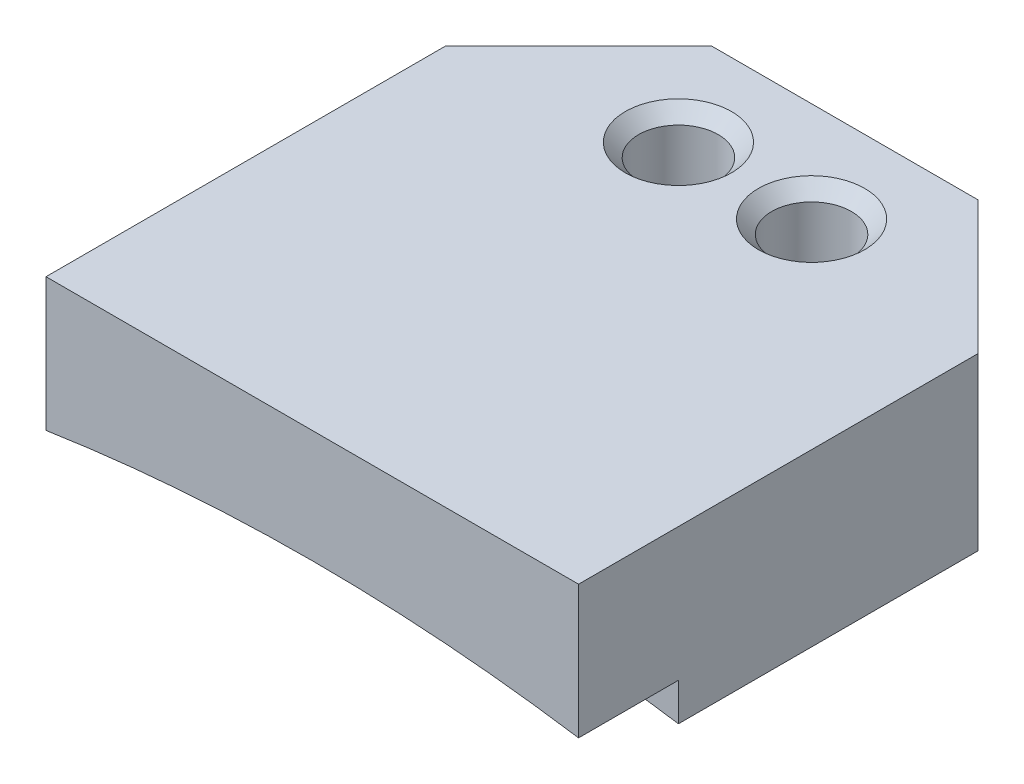
SolidWorks part; units mm, degrees
ref_plane "Front Plane" through (0, 0, 0) normal (0, 0, 1) x (1, 0, 0)
ref_plane "Top Plane" through (0, 0, 0) normal (0, 1, 0) x (1, 0, 0)
ref_plane "Right Plane" through (0, 0, 0) normal (1, 0, 0) x (0, 0, -1)
sketch "Sketch1" plane through (0, 0, 0) normal (0, 1, 0) x (1, 0, 0)
  line L0 (-28.5118, 6.4953) -> (-22.1618, 12.8453)
  line L1 (-22.1618, 12.8453) -> (-9.4618, 12.8453)
  line L2 (-28.5118, 6.4953) -> (-28.5118, -12.5547)
  line L3 (-28.5118, -12.5547) -> (-3.1118, -12.5547)
  line L4 (-3.1118, 6.4953) -> (-3.1118, -12.5547)
  line L5 (-9.4618, 12.8453) -> (-3.1118, 6.4953)
  line L6 (-15.8118, -12.5547) -> (-15.8118, 12.8453) construction
  line L8 (-3.1118, 6.4953) -> (-3.1118, 12.8453) construction
  line L9 (-3.1118, 12.8453) -> (-9.4618, 12.8453) construction
  dimension "D1" = 12.7
  dimension "D2" = 25.4
  dimension "D3" = 25.4
extrude "Boss-Extrude1" add sketch "Sketch1" along normal blind 6.35
sketch "Sketch2" plane through (0, 0, 12.5547) normal (0, 0, 1) x (1, 0, 0)
  circle A0 centre (-15.8118, -82.8523) radius 83.82
  dimension "D1" = 167.64
extrude "Cut-Extrude1" cut sketch "Sketch2" against normal through all both and the other way through all
sketch "Sketch5" plane through (0, 0, -12.8453) normal (0, 0, -1) x (-1, 0, 0)
  line L0 (3.1118, 6.35) -> (3.1118, 0) construction
  line L1 (3.1118, 6.35) -> (3.1118, 0)
  line L4 (28.5118, 6.35) -> (28.5118, 0) construction
  line L5 (28.5118, 6.35) -> (28.5118, 0)
  line L6 (28.5118, -1.7992) -> (28.5118, 0)
  line L7 (3.1118, -1.7992) -> (3.1118, 0)
  line L8 (3.1118, 6.35) -> (28.5118, 6.35)
  arc A0 (3.1118, -1.7992) -> (28.5118, -1.7992) centre (15.8118, -82.8523) cw
  arc A1 (28.5118, 0) -> (3.1118, 0) centre (15.8118, -82.8523) ccw construction
  arc A2 (28.5118, 0) -> (3.1118, 0) centre (15.8118, -82.8523) ccw construction
  dimension "D1" = 82.042
extrude "Boss-Extrude2" add sketch "Sketch5" against normal blind 20.6375
chamfer "Chamfer1" distance 6.35 angle 45 2 edges at (-28.5118, 2.2754, -12.8453) (-3.1118, 2.2754, -12.8453)
hole_wizard "#10-24 Tapped Hole1" positions "Sketch3" profile "Sketch4" tap size "#10-24" standard "ANSI Inch" end condition through all
sketch "Sketch3" plane through (0, 6.35, 0) normal (0, 1, 0) x (1, 0, 0)
  line L0 (-15.8118, 12.8453) -> (-15.8118, 3.4006) construction
  line L1 (-9.4618, 12.8453) -> (-22.1618, 12.8453) construction
  point P0 (-18.9868, 8.0828)
  point P12 (-12.6368, 8.0828)
  dimension "D1" = 4.7625
  dimension "D2" = 3.175
sketch "Sketch4" plane through (-18.9868, 6.35, -8.0828) normal (1, 0, 0) x (0, 0, 1)
  line L0 (0, 0) -> (0, 8.1492)
  line L1 (0, 8.1492) -> (1.8986, 8.1492)
  line L2 (1.8986, 8.1492) -> (1.8986, 0.635)
  line L3 (1.8986, 0.635) -> (2.5337, 0)
  line L5 (2.5337, 0) -> (0, 0)
  line L6 (-1.8986, 0.635) -> (-2.5337, 0) construction
  line L11 (0, -6.35) -> (0, 107.95) construction
  dimension "Thru Tap Drill Dia." = 3.7973
  dimension "Thru Tap Drill Depth" = 8.1492
  dimension "Near C'Sink Dia." = 5.0673
  dimension "Near C'Sink Angle" = 90
cosmetic thread "Hole Thread3" parameters "D2"=4.826
cosmetic thread "Hole Thread4" parameters "D2"=4.826
